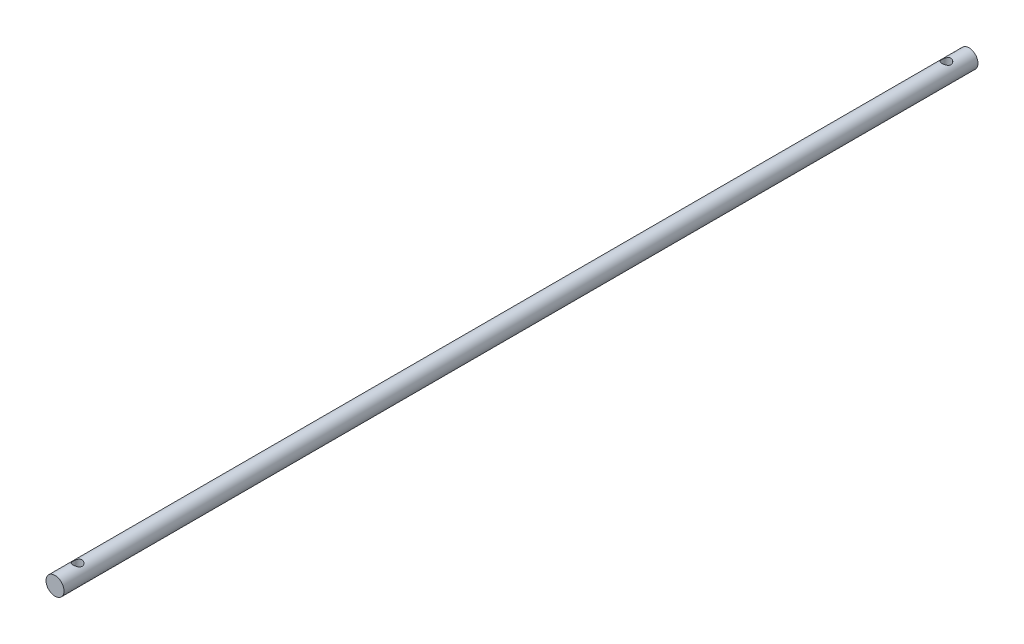
SolidWorks part; units mm, degrees
material "Plain Carbon Steel"
ref_plane "Front Plane" through (0, 0, 0) normal (0, 0, 1) x (1, 0, 0)
ref_plane "Top Plane" through (0, 0, 0) normal (0, 1, 0) x (1, 0, 0)
ref_plane "Right Plane" through (0, 0, 0) normal (1, 0, 0) x (0, 0, -1)
sketch "Sketch1" plane through (0, 0, 0) normal (0, 0, 1) x (1, 0, 0)
  circle A0 centre (0, 0) radius 4
extrude "Extrude1" add sketch "Sketch1" along normal blind 405
hole_wizard "Ø4.0 (4) Diameter Hole1" positions "Sketch4" profile "Sketch3" hole size "Ø4.0" standard "Ansi Metric" end condition through all
sketch "Sketch4" plane through (0, 0, 0) normal (0, 1, 0) x (1, 0, 0)
  line L0 (4, 0) -> (-4, 0) construction
  line L1 (-4, -405) -> (4, -405) construction
  point P1 (0, -10)
  point P3 (0, -395)
  dimension "D1" = 10
  dimension "D2" = 10
sketch "Sketch3" plane through (0, 0, 10) normal (1, 0, 0) x (0, 0, -1)
  line L0 (0, 0) -> (0, 4)
  line L1 (0, 4) -> (2, 4)
  line L2 (2, 4) -> (2, 0)
  line L5 (2, 0) -> (0, 0)
  line L11 (0, -6.35) -> (0, 107.95) construction
  dimension "Thru Hole Dia." = 4
  dimension "Thru Hole Depth" = 4
